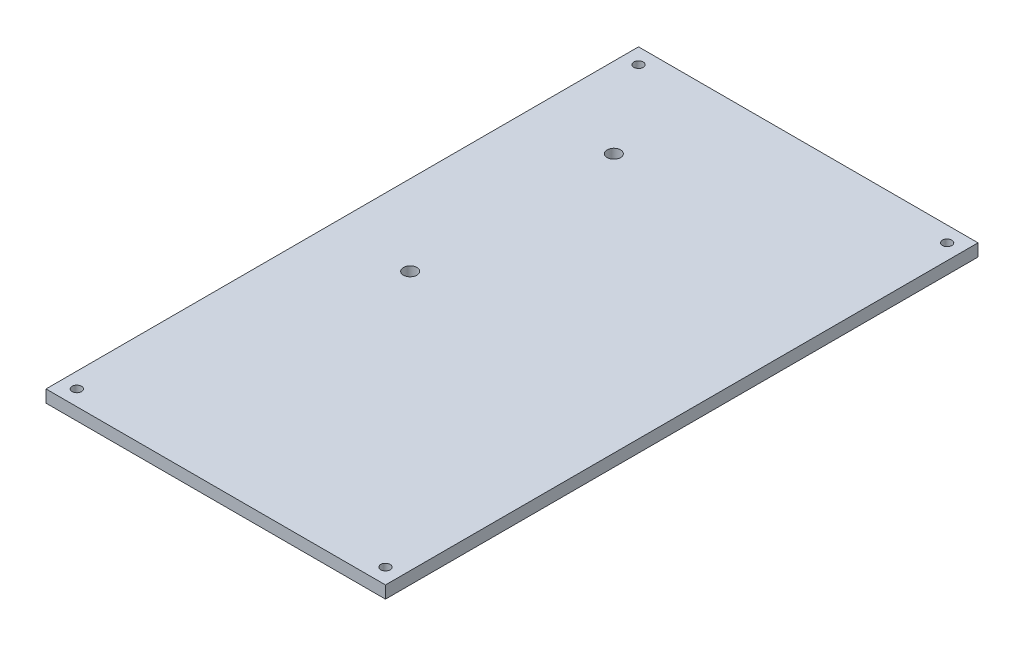
SolidWorks part; units mm, degrees
material "PCB (FR-4) (Recolor)"
ref_plane "Front Plane" through (0, 0, 0) normal (0, 0, 1) x (1, 0, 0)
ref_plane "Top Plane" through (0, 0, 0) normal (0, 1, 0) x (1, 0, 0)
ref_plane "Right Plane" through (0, 0, 0) normal (1, 0, 0) x (0, 0, -1)
sketch "Sketch2" plane through (0, 0, 0) normal (0, 1, 0) x (1, 0, 0)
  line L1 (0, 0) -> (55, 0)
  line L2 (0, 0) -> (0, 96)
  line L3 (0, 96) -> (55, 96)
  line L4 (55, 0) -> (55, 96)
  dimension "D1" = 96
  dimension "D2" = 55
extrude "Boss-Extrude1" add sketch "Sketch2" along normal blind 2
sketch "Sketch3" plane through (0, 2, 0) normal (0, 1, 0) x (1, 0, 0)
  line L0 (2.5, 2.5) -> (52.5, 2.5) construction
  line L1 (52.5, 2.5) -> (52.5, 93.5) construction
  line L2 (0, 0) -> (55, 0) construction
  line L3 (55, 0) -> (55, 96) construction
  line L4 (0, 96) -> (0, 0) construction
  line L5 (55, 96) -> (0, 96) construction
  line L6 (2.5, 93.5) -> (52.5, 93.5) construction
  line L9 (2.5, 93.5) -> (2.5, 2.5) construction
  circle A0 centre (2.5, 2.5) radius 0.762
  circle A1 centre (52.5, 2.5) radius 0.762
  circle A2 centre (52.5, 93.5) radius 0.762
  circle A3 centre (2.5, 93.5) radius 0.762
  dimension "D1" = 1.524
  dimension "D2" = 2.5
  dimension "D3" = 2.5
  dimension "D4" = 2.5
  dimension "D5" = 2.5
extrude "Cut-Extrude1" cut sketch "Sketch3" against normal through all
sketch "Sketch4" plane through (0, 2, 0) normal (0, 1, 0) x (1, 0, 0)
  line L0 (55, 96) -> (0, 96) construction
  line L3 (0, 0) -> (55, 0) construction
  line L7 (0, 96) -> (0, 0) construction
  line L10 (55, 0) -> (55, 96) construction
  line L19 (55, 48) -> (0, 48) construction
  line L20 (5, 91) -> (5, 96) construction
  line L21 (5, 91) -> (0, 91) construction
  line L22 (50, 91) -> (50, 84) construction
  line L23 (21, 84) -> (50, 84) construction
  line L24 (21, 11) -> (21, 84) construction
  line L25 (5, 11) -> (21, 11) construction
  line L26 (5, 91) -> (5, 0) construction
  line L27 (13, 11) -> (13, 96) construction
  line L28 (50, 91) -> (5, 91) construction
  line L29 (5, 94) -> (50, 94) construction
  line L30 (50, 91) -> (50, 96) construction
  line L31 (50, 91) -> (55, 91) construction
  point P23 (13, 79)
  point P27 (13, 46)
  dimension "D1" = 16
  dimension "D2" = 45
  dimension "D3" = 83
  dimension "D4" = 10
  dimension "D5" = 35
  dimension "D6" = 15
  dimension "D7" = 2
hole_wizard "#44 (0.086) Diameter Hole2" positions "Sketch8" profile "Sketch9" hole size "#44" standard "ANSI Inch" end condition through all
sketch "Sketch8" plane through (0, 2, 0) normal (0, 1, 0) x (1, 0, 0)
  point P0 (13, 79)
  point P3 (13, 46)
sketch "Sketch9" plane through (13, 2, -79) normal (1, 0, 0) x (0, 0, 1)
  line L0 (0, 0) -> (0, 2)
  line L1 (0, 2) -> (1.0922, 2)
  line L2 (1.0922, 2) -> (1.0922, 0)
  line L5 (1.0922, 0) -> (0, 0)
  line L11 (0, -6.35) -> (0, 107.95) construction
  dimension "Thru Hole Dia." = 2.1844
  dimension "Thru Hole Depth" = 2
